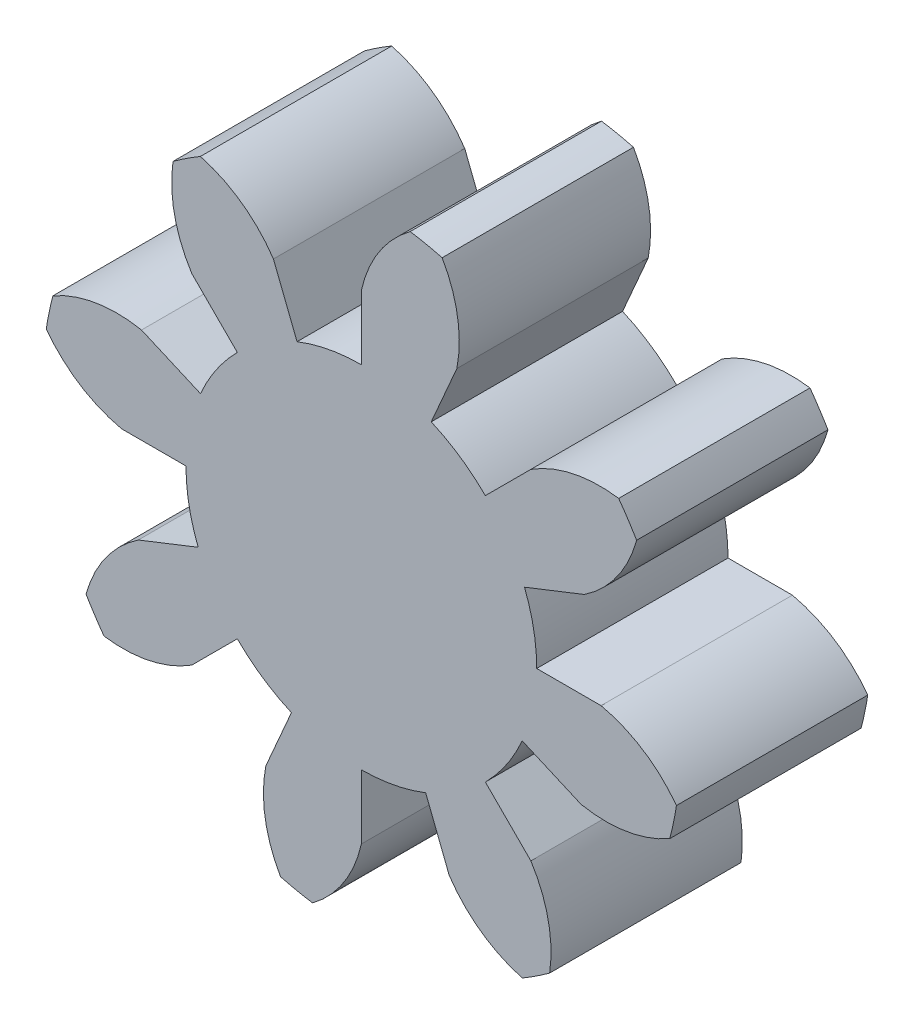
SolidWorks part; units mm, degrees
ref_plane "Plan de face" through (0, 0, 0) normal (0, 0, 1) x (1, 0, 0)
ref_plane "Plan de dessus" through (0, 0, 0) normal (0, 1, 0) x (1, 0, 0)
ref_plane "Plan de droite" through (0, 0, 0) normal (1, 0, 0) x (0, 0, -1)
sketch "Esquisse1" plane through (0, 0, 0) normal (0, 0, 1) x (1, 0, 0)
  circle A0 centre (0, 0) radius 4
  circle A1 centre (0, 0) radius 5
  circle A2 centre (0, 0) radius 2.75
  circle A3 centre (0, 0) radius 3
  circle A4 centre (0, 0) radius 3.7588
  dimension "Pitch Circle" = 8
  dimension "Addendum Circle" = 10
  dimension "Root Circle" = 5.5
  dimension "Clearence Circle" = 6
  dimension "Base Circle" = 7.5175
sketch "Involute" plane through (0, 0, 0) normal (0, 0, 1) x (1, 0, 0)
  line L0 (0, 0) -> (0, 3.7588)
  line L1 (0, 0) -> (1.8794, 3.2552) construction
  line L2 (0, 0) -> (3.2552, 1.8794) construction
  line L3 (0, 0) -> (3.7588, 0) construction
  line L4 (3.7588, 0) -> (3.7588, 5.9043) construction
  line L5 (3.2552, 1.8794) -> (1.2871, 5.2882) construction
  line L6 (1.8794, 3.2552) -> (0.175, 4.2392) construction
  line L7 (0, 0) -> (1.5307, 3.6955) construction
  line L8 (2.8284, 2.8284) -> (0, 0)
  line L9 (0.8141, 3.9163) -> (0, 0) construction
  circle A0 centre (0, 0) radius 3.7588 construction
  circle A1 centre (0, 0) radius 4 construction
  arc A2 (1.5307, 3.6955) -> (0.0689, 3.9994) centre (0, 0) ccw
  spline S0 degree 3 poles (0, 3.7588) (0.3306, 5.298) (2.4903, 5.9063) (3.7588, 5.9043) knots 0 0 0 0 1 1 1 1
  spline S1 degree 3 poles (1.498, 3.4474) (1.8082, 4.9909) (0.0699, 6.4094) (-1.0943, 6.9131) knots 0 0 0 0 1 1 1 1
  dimension "Involute Control" = 90
  dimension "Base Circle Quarter Circumference" = 5.9043
  dimension "D1" = 3.9362
  dimension "D2" = 1.9681
  dimension "Circular Pitch" = 45
  dimension "Involute Array" = 4
sketch "Esquisse4" plane through (0, 0, 0) normal (0, 0, 1) x (1, 0, 0)
  line L0 (0, 0) -> (0, 3.7588) construction
  line L1 (0, 3.7588) -> (0, 2.75)
  line L2 (1.498, 3.4474) -> (1.096, 2.5222)
  arc A0 (0.7655, 4.9411) -> (1.2671, 4.8368) centre (0, 0) cw
  circle A1 centre (0, 0) radius 5 construction
  arc A2 (0, 2.75) -> (1.096, 2.5222) centre (0, 0) cw
  circle A3 centre (0, 0) radius 2.75 construction
  arc A4 (0, 3.7588) -> (0.7655, 4.9411) centre (1.9627, 3.3269) cw
  arc A5 (1.2671, 4.8368) -> (1.498, 3.4474) centre (-0.4742, 3.8335) cw
  spline S0 degree 3 poles (0, 3.7588) (0.3306, 5.298) (2.4903, 5.9063) (3.7588, 5.9043) knots 0 0 0 0 1 1 1 1 construction
  spline S1 degree 3 poles (1.498, 3.4474) (1.8082, 4.9909) (0.0699, 6.4094) (-1.0943, 6.9131) knots 0 0 0 0 1 1 1 1 construction
extrude "Boss.-Extru.1" add sketch "Esquisse4" along normal blind 3
ref_axis "Axe1" through (0, 0, 0) along (0, 0, 1)
pattern_circular "Répétition circulaire2" count 8 over 360 about axis through (0, 0, 0) along (0, 0, 1) of bodies 101
sketch "Esquisse5" plane through (0, 0, 0) normal (0, 0, 1) x (1, 0, 0)
  circle A0 centre (0, 0) radius 2.75 construction
  circle A1 centre (0, 0) radius 2.75
extrude "Boss.-Extru.2" add sketch "Esquisse5" along normal up to surface (3 mm away) up to face at (-3.7348, 0.7764, 3)
equation "\"Module\" = 1"
equation "\"Nb de dents\"= 8"
equation "\"Pressure Angle\"= 20"
equation "\"Pitch Circle@Esquisse1\"= \"Module\" * \"Nb de dents\""
equation "\"Addendum Circle@Esquisse1\"= \"Pitch Circle@Esquisse1\" + ( \"Module\" * 2 )"
equation "\"Clearence Circle@Esquisse1\"= \"Pitch Circle@Esquisse1\" - ( \"Module\" * 2 )"
equation "\"Root Circle@Esquisse1\"= \"Pitch Circle@Esquisse1\" - ( ( \"Module\" * 1.25 ) * 2 )"
equation "\"Base Circle@Esquisse1\"= \"Pitch Circle@Esquisse1\" * cos ( \"Pressure Angle\" )"
equation "\"Base Circle Quarter Circumference@Involute\" = \"Base Circle@Esquisse1\" * pI / 4"
equation "\"D1@Involute\"=\"Base Circle Quarter Circumference@Involute\"/3*2"
equation "\"D2@Involute\"=\"Base Circle Quarter Circumference@Involute\"/3"
equation "\"Circular Pitch@Involute\"=360/\"Nb de dents\""
equation "\"D1@Répétition circulaire2\"= \"Nb de dents\""
